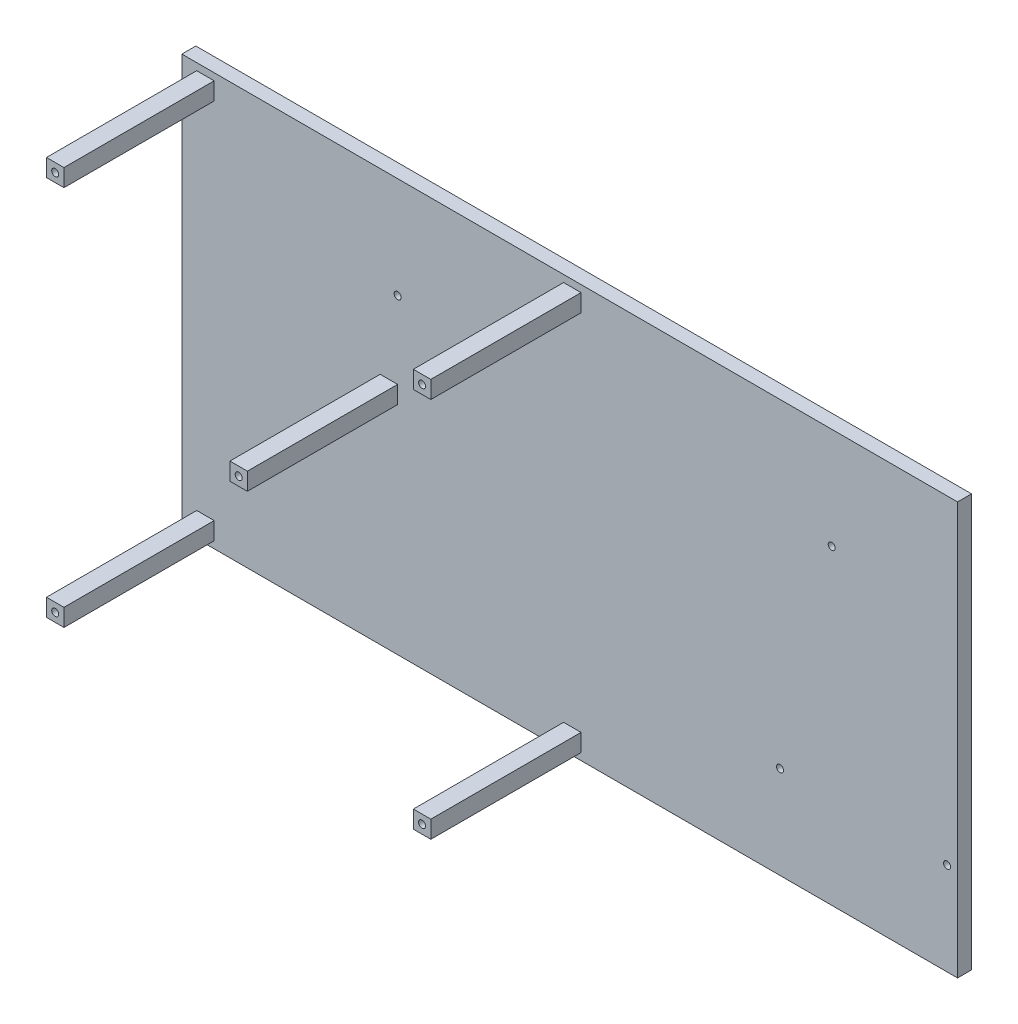
SolidWorks part; units mm, degrees
ref_plane "Alzado" through (0, 0, 0) normal (0, 0, 1) x (1, 0, 0)
ref_plane "Planta" through (0, 0, 0) normal (0, 1, 0) x (1, 0, 0)
ref_plane "Vista lateral" through (0, 0, 0) normal (1, 0, 0) x (0, 0, -1)
sketch "Sketch1" plane through (0, 0, 0) normal (0, 0, 1) x (1, 0, 0)
  line L1 (-99.7768, 38.058) -> (100.2232, 38.058)
  line L2 (-99.7768, 38.058) -> (-99.7768, -111.942)
  line L3 (-99.7768, -111.942) -> (100.2232, -111.942)
  line L4 (100.2232, 38.058) -> (100.2232, -111.942)
  dimension "D1" = 200
  dimension "D2" = 150
extrude "Boss-Extrude1" add sketch "Sketch1" along normal blind 4
sketch "Sketch2" plane through (100.2232, 0, 0) normal (1, 0, 0) x (0, 0, -1)
  line L1 (-4, 38.058) -> (0, 38.058)
  line L2 (-4, 38.058) -> (-4, -111.942)
  line L3 (-4, -111.942) -> (0, -111.942)
  line L4 (0, 38.058) -> (0, -111.942)
extrude "Boss-Extrude2" add sketch "Sketch2" along normal blind 50
sketch "Sketch3" plane through (0, 0, 0) normal (0, 0, -1) x (-1, 0, 0)
  line L0 (99.7768, 38.058) -> (99.7768, -111.942) construction
  line L1 (99.7768, -111.942) -> (-150.2232, -111.942) construction
  circle A0 centre (96.7768, -77.942) radius 1
  dimension "D1" = 3
  dimension "D2" = 34
extrude "Cut-Extrude1" cut sketch "Sketch3" against normal blind 21
sketch "Sketch4" plane through (0, 0, 0) normal (0, 0, -1) x (-1, 0, 0)
  line L0 (-150.2232, -111.942) -> (-150.2232, 38.058) construction
  circle A0 centre (-147.2232, -77.942) radius 1
  dimension "D1" = 3
extrude "Cut-Extrude2" cut sketch "Sketch4" against normal blind 21
sketch "Sketch5" plane through (0, 0, 0) normal (0, 0, -1) x (-1, 0, 0)
  circle A0 centre (-99.4232, -77.942) radius 1
  circle A1 centre (-147.2232, -77.942) radius 1 construction
  dimension "D1" = 47.8
extrude "Cut-Extrude3" cut sketch "Sketch5" against normal blind 21
sketch "Sketch6" plane through (0, 0, 4) normal (0, 0, 1) x (1, 0, 0)
  line L0 (150.2232, -111.942) -> (150.2232, -15.442) construction
  line L1 (150.2232, 38.058) -> (150.2232, -111.942) construction
  line L2 (150.2232, -15.442) -> (114.2032, -15.442) construction
  circle A0 centre (114.2032, -15.442) radius 1
  circle A1 centre (-10.0268, -15.442) radius 1
  dimension "D3" = 124.23
  dimension "D1" = 96.5
  dimension "D2" = 36.02
extrude "Cut-Extrude4" cut sketch "Sketch6" against normal through all
sketch "Sketch7" plane through (0, 0, 0) normal (0, 0, -1) x (-1, 0, 0)
  circle A0 centre (93.6327, -80.2492) radius 6.1441
extrude "Boss-Extrude3" add sketch "Sketch7" against normal blind 4
sketch "Sketch8" plane through (0, 0, 4) normal (0, 0, 1) x (1, 0, 0)
  line L0 (-10.0268, -15.442) -> (-10.0268, 11.558) construction
  line L1 (114.2032, -15.442) -> (113.837, 9.058) construction
  line L2 (-12.5268, 11.558) -> (-7.5268, 11.558)
  line L3 (-12.5268, 11.558) -> (-12.5268, 6.558)
  line L4 (-12.5268, 6.558) -> (-7.5268, 6.558)
  line L5 (-7.5268, 11.558) -> (-7.5268, 6.558)
  line L6 (-12.5268, 11.558) -> (-7.5268, 6.558) construction
  line L7 (-12.5268, 6.558) -> (-7.5268, 11.558) construction
  line L8 (116.337, 6.558) -> (111.337, 6.558)
  line L9 (116.337, 6.558) -> (116.337, 11.558)
  line L10 (116.337, 11.558) -> (111.337, 11.558)
  line L11 (111.337, 6.558) -> (111.337, 11.558)
  line L12 (116.337, 6.558) -> (111.337, 11.558) construction
  line L13 (116.337, 11.558) -> (111.337, 6.558) construction
  point P3 (-10.0268, 9.058)
  point P8 (113.837, 9.058)
  dimension "D1" = 27
  dimension "D2" = 5
  dimension "D3" = 5
  dimension "D4" = 2.5
  dimension "D5" = 5
extrude "Boss-Extrude4" add sketch "Sketch8" along normal blind 43
sketch "Sketch9" plane through (0, 0, 4) normal (0, 0, 1) x (1, 0, 0)
  line L1 (37.4732, 11.558) -> (42.4732, 11.558)
  line L2 (37.4732, 11.558) -> (37.4732, 6.558)
  line L3 (37.4732, 6.558) -> (42.4732, 6.558)
  line L4 (42.4732, 11.558) -> (42.4732, 6.558)
  line L5 (37.4732, 11.558) -> (42.4732, 6.558) construction
  line L6 (37.4732, 6.558) -> (42.4732, 11.558) construction
  point P0 (39.9732, 9.058)
  dimension "D1" = 5
  dimension "D2" = 45
extrude "Boss-Extrude5" add sketch "Sketch9" along normal blind 43
sketch "Sketch10" plane through (0, 0, 4) normal (0, 0, 1) x (1, 0, 0)
  line L1 (-67.5268, 11.558) -> (-62.5268, 11.558)
  line L2 (-67.5268, 11.558) -> (-67.5268, 6.558)
  line L3 (-67.5268, 6.558) -> (-62.5268, 6.558)
  line L4 (-62.5268, 11.558) -> (-62.5268, 6.558)
  line L5 (-67.5268, 11.558) -> (-62.5268, 6.558) construction
  line L6 (-67.5268, 6.558) -> (-62.5268, 11.558) construction
  point P0 (-65.0268, 9.058)
  dimension "D1" = 5
  dimension "D2" = 50
extrude "Boss-Extrude6" add sketch "Sketch10" along normal blind 43
sketch "Sketch11" plane through (0, 0, 4) normal (0, 0, 1) x (1, 0, 0)
  line L0 (-99.7768, -111.942) -> (150.2232, -111.942) construction
  line L1 (-99.7768, 38.058) -> (-69.7768, 38.058)
  line L2 (-99.7768, 38.058) -> (-99.7768, -111.942)
  line L3 (-99.7768, -111.942) -> (-69.7768, -111.942)
  line L4 (-69.7768, 38.058) -> (-69.7768, -111.942)
  line L5 (150.2232, 38.058) -> (150.2232, -111.942) construction
  dimension "D1" = 220
extrude "Cut-Extrude5" cut sketch "Sketch11" against normal blind 10
sketch "Sketch12" plane through (0, 0, 4) normal (0, 0, 1) x (1, 0, 0)
  line L0 (150.2232, 38.058) -> (150.2232, -111.942) construction
  line L1 (-69.7768, 38.058) -> (150.2232, 38.058)
  line L2 (-69.7768, 38.058) -> (-69.7768, 13.558)
  line L3 (-69.7768, 13.558) -> (150.2232, 13.558)
  line L4 (150.2232, 38.058) -> (150.2232, 13.558)
  line L5 (-7.5268, 11.558) -> (-12.5268, 11.558) construction
  dimension "D1" = 2
extrude "Cut-Extrude6" cut sketch "Sketch12" against normal blind 10
sketch "Sketch13" plane through (0, 0, 47) normal (0, 0, 1) x (1, 0, 0)
  line L0 (-69.7768, 13.558) -> (150.2232, 13.558) construction
  line L1 (141.9311, -10.2341) -> (101.0556, -10.2341)
  line L2 (141.9311, -10.2341) -> (141.9311, 13.558)
  line L3 (141.9311, 13.558) -> (101.0556, 13.558)
  line L4 (101.0556, -10.2341) -> (101.0556, 13.558)
  line L5 (141.9311, -10.2341) -> (101.0556, 13.558) construction
  line L6 (141.9311, 13.558) -> (101.0556, -10.2341) construction
  line L8 (9.9273, -16.0886) -> (-20.8496, -16.0886)
  line L9 (9.9273, -16.0886) -> (9.9273, 16.0886)
  line L10 (9.9273, 16.0886) -> (-20.8496, 16.0886)
  line L11 (-20.8496, -16.0886) -> (-20.8496, 16.0886)
  line L12 (9.9273, -16.0886) -> (-20.8496, 16.0886) construction
  line L13 (9.9273, 16.0886) -> (-20.8496, -16.0886) construction
  point P0 (121.4933, 1.662)
  point P7 (-5.4612, 0)
extrude "Cut-Extrude7" cut sketch "Sketch13" against normal up to vertex (43 mm away) up to point (-69.7768, 13.558, 4)
sketch "Sketch14" plane through (0, 0, 4) normal (0, 0, 1) x (1, 0, 0)
  line L0 (150.2232, 13.558) -> (150.2232, -111.942) construction
  line L1 (-69.7768, -111.942) -> (150.2232, -111.942)
  line L2 (-69.7768, -111.942) -> (-69.7768, -104.442)
  line L3 (-69.7768, -104.442) -> (150.2232, -104.442)
  line L4 (150.2232, -111.942) -> (150.2232, -104.442)
  dimension "D1" = 7.5
extrude "Cut-Extrude8" cut sketch "Sketch14" against normal blind 10
sketch "Sketch15" plane through (0, 0, 0) normal (0, 0, -1) x (-1, 0, 0)
  line L1 (69.7768, -104.442) -> (71.7768, -104.442)
  line L2 (69.7768, -104.442) -> (69.7768, 13.558)
  line L3 (69.7768, 13.558) -> (71.7768, 13.558)
  line L4 (71.7768, -104.442) -> (71.7768, 13.558)
  dimension "D1" = 2
extrude "Boss-Extrude7" add sketch "Sketch15" against normal blind 47
sketch "Sketch17" plane through (-71.7768, 0, 0) normal (-1, 0, 0) x (0, 0, 1)
  line L0 (0, -104.442) -> (0, -45.442) construction
  line L1 (0, -104.442) -> (0, 13.558) construction
  line L2 (0, -45.442) -> (10, -45.442) construction
  line L4 (6.5, -41.942) -> (13.5, -41.942)
  line L5 (6.5, -41.942) -> (6.5, -48.942)
  line L6 (6.5, -48.942) -> (13.5, -48.942)
  line L7 (13.5, -41.942) -> (13.5, -48.942)
  line L8 (6.5, -41.942) -> (13.5, -48.942) construction
  line L9 (6.5, -48.942) -> (13.5, -41.942) construction
  dimension "D1" = 59
  dimension "D2" = 10
  dimension "D3" = 7
  dimension "D4" = 7
extrude "Boss-Extrude8" add sketch "Sketch17" against normal blind 10
sketch "Sketch18" plane through (-71.7768, 0, 0) normal (-1, 0, 0) x (0, 0, 1)
  circle A0 centre (10, -45.442) radius 2.5
extrude "Cut-Extrude9" cut sketch "Sketch18" against normal blind 9
sketch "Sketch19" plane through (-62.7768, 0, 0) normal (-1, 0, 0) x (0, 0, 1)
  circle A0 centre (10, -45.442) radius 1
extrude "Boss-Extrude9" add sketch "Sketch19" along normal blind 9 separate body
fillet "Fillet1" radius 1 1 edges at (-71.7768, -45.442, 11)
sketch "Sketch20" plane through (-71.7768, 0, 0) normal (-1, 0, 0) x (0, 0, 1)
  line L1 (13.3193, -82.942) -> (6.1193, -82.942)
  line L2 (13.3193, -82.942) -> (13.3193, -97.442)
  line L3 (13.3193, -97.442) -> (6.1193, -97.442)
  line L4 (6.1193, -82.942) -> (6.1193, -97.442)
  dimension "D1" = 14.5
  dimension "D2" = 34
  dimension "D3" = 7.2
extrude "Boss-Extrude10" add sketch "Sketch20" against normal up to vertex (10 mm away) up to point (-61.7768, -48.942, 6.5)
sketch "Sketch21" plane through (-71.7768, 0, 0) normal (-1, 0, 0) x (0, 0, 1)
  line L1 (12.2701, -84.005) -> (7.3078, -84.005)
  line L2 (12.2701, -84.005) -> (12.2701, -96.3789)
  line L3 (12.2701, -96.3789) -> (7.3078, -96.3789)
  line L4 (7.3078, -84.005) -> (7.3078, -96.3789)
  line L5 (12.2701, -84.005) -> (7.3078, -96.3789) construction
  line L6 (12.2701, -96.3789) -> (7.3078, -84.005) construction
  point P0 (9.7889, -90.192)
extrude "Cut-Extrude10" cut sketch "Sketch21" against normal blind 9
sketch "Sketch22" plane through (-62.7768, 0, 0) normal (-1, 0, 0) x (0, 0, 1)
  line L0 (12.2701, -90.192) -> (7.3078, -90.192) construction
  line L1 (12.2701, -96.3789) -> (12.2701, -84.005) construction
  line L2 (7.3078, -84.005) -> (7.3078, -96.3789) construction
  line L3 (9.7889, -84.005) -> (9.7889, -90.192) construction
  line L4 (12.2701, -84.005) -> (7.3078, -84.005) construction
  line L6 (9.4002, -85.5769) -> (10.1776, -85.5769)
  line L7 (9.4002, -85.5769) -> (9.4002, -94.8071)
  line L8 (9.4002, -94.8071) -> (10.1776, -94.8071)
  line L9 (10.1776, -85.5769) -> (10.1776, -94.8071)
  line L10 (9.4002, -85.5769) -> (10.1776, -94.8071) construction
  line L11 (9.4002, -94.8071) -> (10.1776, -85.5769) construction
extrude "Boss-Extrude11" add sketch "Sketch22" along normal blind 8
sketch "Sketch23" plane through (-62.7768, 0, 0) normal (-1, 0, 0) x (0, 0, 1)
  line L0 (10.1776, -94.8071) -> (10.1776, -85.5769) construction
  line L1 (10.1776, -85.9244) -> (10.7685, -85.9244)
  line L2 (10.1776, -85.9244) -> (10.1776, -86.7244)
  line L3 (10.1776, -86.7244) -> (10.7685, -86.7244)
  line L4 (10.7685, -85.9244) -> (10.7685, -86.7244)
  line L5 (10.1776, -94.8071) -> (10.1776, -85.5769) construction
  line L6 (10.1776, -88.8258) -> (10.7685, -88.8258)
  line L7 (10.1776, -88.8258) -> (10.1776, -87.9896)
  line L8 (10.1776, -87.9896) -> (10.7685, -87.9896)
  line L9 (10.7685, -88.8258) -> (10.7685, -87.9896)
  line L11 (10.1776, -91.0887) -> (10.7685, -91.0887)
  line L12 (10.1776, -91.0887) -> (10.1776, -91.8758)
  line L13 (10.1776, -91.8758) -> (10.7685, -91.8758)
  line L14 (10.7685, -91.0887) -> (10.7685, -91.8758)
  line L15 (10.1776, -93.3024) -> (10.7685, -93.3024)
  line L16 (10.1776, -93.3024) -> (10.1776, -94.1387)
  line L17 (10.1776, -94.1387) -> (10.7685, -94.1387)
  line L18 (10.7685, -93.3024) -> (10.7685, -94.1387)
  dimension "D1" = 0.8
extrude "Boss-Extrude12" add sketch "Sketch23" along normal blind 7
sketch "Sketch24" plane through (0, 0, 4) normal (0, 0, 1) x (1, 0, 0)
  line L0 (42.4732, 6.558) -> (42.4732, -37.442) construction
  line L2 (42.4732, -37.442) -> (37.4732, -37.442)
  line L3 (42.4732, -37.442) -> (42.4732, -42.442)
  line L4 (42.4732, -42.442) -> (37.4732, -42.442)
  line L5 (37.4732, -37.442) -> (37.4732, -42.442)
  dimension "D1" = 44
  dimension "D2" = 5
extrude "Boss-Extrude13" add sketch "Sketch24" along normal up to vertex (43 mm away) up to point (42.4732, 6.558, 47)
sketch "Sketch25" plane through (0, 0, 4) normal (0, 0, 1) x (1, 0, 0)
  line L0 (42.4732, 6.558) -> (42.4732, -63.442) construction
  line L1 (37.4732, -68.442) -> (-67.5268, -68.442) construction
  line L2 (42.4732, -63.442) -> (37.4732, -63.442)
  line L3 (42.4732, -63.442) -> (42.4732, -68.442)
  line L4 (42.4732, -68.442) -> (37.4732, -68.442)
  line L5 (37.4732, -63.442) -> (37.4732, -68.442)
  line L7 (-67.5268, -68.442) -> (-62.5268, -68.442)
  line L8 (-67.5268, -68.442) -> (-67.5268, -63.442)
  line L9 (-67.5268, -63.442) -> (-62.5268, -63.442)
  line L10 (-62.5268, -68.442) -> (-62.5268, -63.442)
  dimension "D1" = 70
  dimension "D2" = 5
  dimension "D3" = 5
  dimension "D4" = 5
extrude "Boss-Extrude14" add sketch "Sketch25" along normal up to vertex (43 mm away) up to point (37.4732, -42.442, 47)
sketch "Sketch26" plane through (0, 0, 47) normal (0, 0, 1) x (1, 0, 0)
  line L1 (42.4732, -42.442) -> (37.4732, -42.442)
  line L2 (42.4732, -42.442) -> (42.4732, -37.442)
  line L3 (42.4732, -37.442) -> (37.4732, -37.442)
  line L4 (37.4732, -42.442) -> (37.4732, -37.442)
extrude "Cut-Extrude11" cut sketch "Sketch26" against normal up to vertex (43 mm away) up to point (42.4732, -42.442, 4)
sketch "Sketch27" plane through (0, 0, 4) normal (0, 0, 1) x (1, 0, 0)
  line L0 (150.2232, -104.442) -> (-69.7768, -104.442) construction
  line L1 (42.4732, -102.442) -> (37.4732, -102.442)
  line L2 (42.4732, -102.442) -> (42.4732, -97.442)
  line L3 (42.4732, -97.442) -> (37.4732, -97.442)
  line L4 (37.4732, -102.442) -> (37.4732, -97.442)
  line L5 (42.4732, 6.558) -> (42.4732, -104.442) construction
  dimension "D1" = 5
  dimension "D2" = 5
  dimension "D3" = 2
  dimension "D4" = 5
extrude "Boss-Extrude15" add sketch "Sketch27" along normal up to vertex (43 mm away) up to point (37.4732, -68.442, 47)
sketch "Sketch28" plane through (0, 0, 47) normal (0, 0, 1) x (1, 0, 0)
  line L1 (37.4732, -63.442) -> (42.4732, -63.442)
  line L2 (37.4732, -63.442) -> (37.4732, -68.442)
  line L3 (37.4732, -68.442) -> (42.4732, -68.442)
  line L4 (42.4732, -63.442) -> (42.4732, -68.442)
extrude "Cut-Extrude12" cut sketch "Sketch28" against normal up to vertex (43 mm away) up to point (42.4732, -68.442, 4)
sketch "Sketch29" plane through (0, 0, 47) normal (0, 0, 1) x (1, 0, 0)
  line L0 (-71.7768, -104.442) -> (-71.7768, 13.558) construction
  line L1 (-69.7768, -104.442) -> (-71.7768, -104.442)
  line L2 (-69.7768, -104.442) -> (-69.7768, -38.032)
  line L3 (-69.7768, -38.032) -> (-71.7768, -38.032)
  line L4 (-71.7768, -104.442) -> (-71.7768, -38.032)
extrude "Boss-Extrude16" add sketch "Sketch29" against normal up to vertex (47 mm away) up to point (-71.7768, -104.442, 0)
sketch "Sketch30" plane through (0, 0, 13.5) normal (0, 0, 1) x (1, 0, 0)
  line L0 (-69.7768, -104.442) -> (-69.7768, 13.558) construction
  line L1 (-61.7768, -41.942) -> (-69.7768, -41.942)
  line L2 (-61.7768, -41.942) -> (-61.7768, -48.942)
  line L3 (-61.7768, -48.942) -> (-69.7768, -48.942)
  line L4 (-69.7768, -41.942) -> (-69.7768, -48.942)
  line L5 (-61.7768, -82.942) -> (-69.7768, -82.942)
  line L6 (-61.7768, -82.942) -> (-61.7768, -97.442)
  line L7 (-61.7768, -97.442) -> (-69.7768, -97.442)
  line L8 (-69.7768, -82.942) -> (-69.7768, -97.442)
  line L9 (-61.7768, -97.442) -> (-69.7768, -97.442) construction
extrude "Cut-Extrude13" cut sketch "Sketch30" against normal up to vertex (7.3807 mm away) up to point (-61.7768, -97.442, 6.1193)
sketch "Sketch31" plane through (0, 0, 47) normal (0, 0, 1) x (1, 0, 0)
  line L1 (-62.5268, -63.442) -> (-67.5268, -63.442)
  line L2 (-62.5268, -63.442) -> (-62.5268, -68.442)
  line L3 (-62.5268, -68.442) -> (-67.5268, -68.442)
  line L4 (-67.5268, -63.442) -> (-67.5268, -68.442)
extrude "Cut-Extrude14" cut sketch "Sketch31" against normal up to vertex (43 mm away) up to point (-62.5268, -68.442, 4)
sketch "Sketch32" plane through (0, 0, 4) normal (0, 0, 1) x (1, 0, 0)
  line L0 (-67.5268, 6.558) -> (-67.5268, -102.442) construction
  line L1 (150.2232, -104.442) -> (-69.7768, -104.442) construction
  line L2 (-67.5268, -102.442) -> (-62.5268, -102.442)
  line L3 (-67.5268, -102.442) -> (-67.5268, -97.442)
  line L4 (-67.5268, -97.442) -> (-62.5268, -97.442)
  line L5 (-62.5268, -102.442) -> (-62.5268, -97.442)
  dimension "D1" = 5
  dimension "D2" = 5
  dimension "D3" = 2
extrude "Boss-Extrude17" add sketch "Sketch32" along normal up to vertex (43 mm away) up to point (37.4732, -102.442, 47)
sketch "Sketch35" plane through (0, 0, 4) normal (0, 0, 1) x (1, 0, 0)
  line L0 (42.4732, 6.558) -> (42.4732, -37.442) construction
  line L3 (-10.0268, -37.442) -> (-15.0268, -37.442)
  line L4 (-10.0268, -37.442) -> (-10.0268, -42.442)
  line L5 (-10.0268, -42.442) -> (-15.0268, -42.442)
  line L6 (-15.0268, -37.442) -> (-15.0268, -42.442)
  dimension "D1" = 44
  dimension "D2" = 52.5
  dimension "D3" = 5
  dimension "D4" = 5
extrude "Boss-Extrude18" add sketch "Sketch35" along normal up to vertex (43 mm away) up to point (42.4732, -102.442, 47)
sketch "Sketch37" plane through (0, 0, 47) normal (0, 0, 1) x (1, 0, 0)
  circle A0 centre (39.9732, 9.058) radius 1
  circle A1 centre (39.9732, -99.942) radius 1
  circle A2 centre (-65.0268, -99.942) radius 1
  circle A3 centre (-65.0268, 9.058) radius 1
  circle A4 centre (-12.5268, -39.942) radius 1
extrude "Cut-Extrude16" cut sketch "Sketch37" against normal blind 3
sketch "Sketch38" plane through (0, 0, 47) normal (0, 0, 1) x (1, 0, 0)
  line L1 (-71.7768, 13.558) -> (-69.7768, 13.558)
  line L2 (-71.7768, 13.558) -> (-71.7768, -104.442)
  line L3 (-71.7768, -104.442) -> (-69.7768, -104.442)
  line L4 (-69.7768, 13.558) -> (-69.7768, -104.442)
extrude "Cut-Extrude17" cut sketch "Sketch38" against normal up to vertex (43 mm away) up to point (-69.7768, -104.442, 4)
